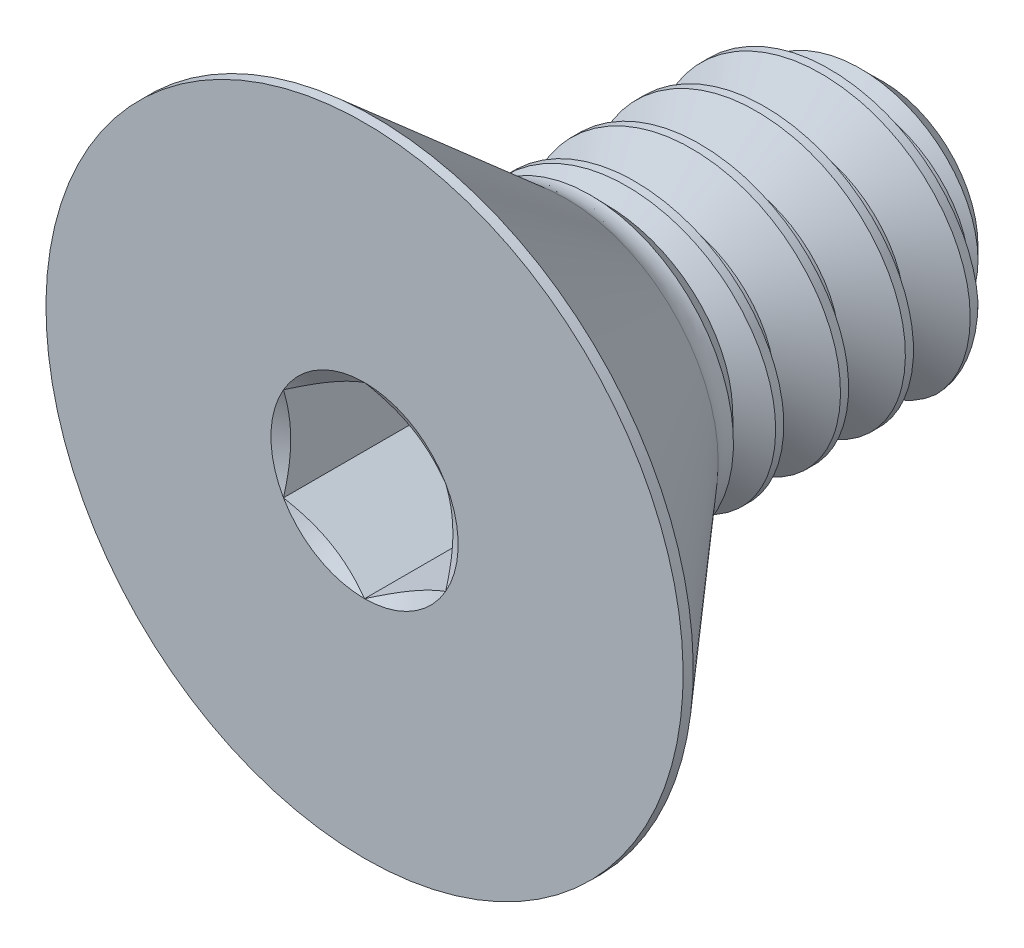
SolidWorks part; units mm, degrees
ref_plane "Front" through (0, 0, 0) normal (0, 0, 1) x (1, 0, 0)
ref_plane "Top" through (0, 0, 0) normal (0, 1, 0) x (1, 0, 0)
ref_plane "Right" through (0, 0, 0) normal (1, 0, 0) x (0, 0, -1)
sketch "Sketch1" plane through (0, 0, 0) normal (1, 0, 0) x (0, 0, -1)
  line L0 (0, 3.8989) -> (0.1232, 3.8989) construction
  line L1 (0.1232, 3.8989) -> (2.4638, 1.8642) construction
  line L2 (0, 1.7526) -> (6.35, 1.7526)
  line L3 (6.35, 1.7526) -> (6.35, 0)
  line L4 (6.35, 0) -> (0, 0)
  line L5 (0, 0) -> (0, 3.8989) construction
  line L6 (0, 3.8989) -> (0, -3.8989) construction
  line L7 (6.35, 1.7526) -> (6.35, -1.7526) construction
  line L8 (0, -3.8989) -> (0.1232, -3.8989) construction
  line L9 (0.1232, -3.8989) -> (2.4638, -1.8642) construction
  line L11 (0, 1.7526) -> (0, 0)
  line L12 (2.7624, 1.7526) -> (2.7624, 0) construction
  line L13 (-19.05, 0) -> (-19.05, 1.7526) construction
  arc A1 (2.4638, 1.8642) -> (2.7624, 1.7526) centre (2.7624, 2.2077) ccw construction
  dimension "D1" = 0.1232
  dimension "Head Ht" = 2.4638
  dimension "Head Dia" = 7.7978
  dimension "Dia" = 3.5052
  dimension "Lg" = 6.35
  dimension "Head Angle" = 82
  dimension "Min Thread" = 25.4
revolve "Revolve1" add sketch "Sketch1" angle 360 about L4
sketch "Sketch3" plane through (0, 0, -6.35) normal (0, 0, -1) x (-1, 0, 0)
  circle A0 centre (0, 0) radius 1.7526
curve "Helix/Spiral1" pitch 0.7937 height 6.35 radius 1.7526 centre (0, 0, -6.35) axis (0, 0, 1) start towards (0, 1, 0)
sketch "Sketch2" plane through (0, 0, 0) normal (1, 0, 0) x (0, 0, -1)
  line L0 (6.35, 1.7526) -> (7.0445, 1.7526)
  line L1 (7.0445, 1.7526) -> (6.7469, 1.237)
  line L2 (6.7469, 1.237) -> (6.6477, 1.237)
  line L3 (6.6477, 1.237) -> (6.35, 1.7526)
  line L4 (6.4988, 1.4948) -> (6.8957, 1.4948) construction
  dimension "D1" = 60
  dimension "D2" = 0.0992
  dimension "D3" = 0.3969
ref_plane "Plane2" through (0, 0, 19.05) normal (0, 0, 1) x (1, 0, 0)
chamfer "Chamfer1" distance 0.5953 angle 45 1 edges at (0, 1.7526, -6.35)
sweep "Cut-Sweep1" cut profiles "Sketch2" path "Helix/Spiral1"
sketch "Sketch7" plane through (0, 0, 0) normal (1, 0, 0) x (0, 0, -1)
  line L0 (0, 3.8989) -> (0.1232, 3.8989) construction
  line L1 (0.1232, 3.8989) -> (2.4638, 1.8642) construction
  line L2 (0, 3.8989) -> (0.1232, 3.8989)
  line L3 (0.1232, 3.8989) -> (2.4638, 1.8642)
  line L4 (2.7624, 1.7526) -> (2.7624, 0) construction
  line L5 (2.7624, 1.7526) -> (2.7624, 0)
  line L7 (0, 0) -> (0, 3.8989) construction
  line L8 (0, 0) -> (0, 3.8989)
  line L9 (0, 0) -> (2.7624, 0)
  line L10 (5.7417, 0) -> (-5.7417, 0) construction
  arc A0 (2.4638, 1.8642) -> (2.7624, 1.7526) centre (2.7624, 2.2077) ccw construction
  arc A1 (2.4638, 1.8642) -> (2.7624, 1.7526) centre (2.7624, 2.2077) ccw
revolve "Revolve2" add sketch "Sketch7" angle 360 about L9
ref_plane "Plane1" through (0, 0, -2.7624) normal (0, 0, 1) x (1, 0, 0)
sketch "Sketch8" plane through (0, 0, -2.7624) normal (0, 0, 1) x (1, 0, 0)
  circle A0 centre (0, 0) radius 1.7526
extrude "Boss-Extrude1" add sketch "Sketch8" against normal through all draft 46
sketch "Sketch5" plane through (0, 0, 0) normal (0, 0, 1) x (1, 0, 0)
  line L0 (0, 0) -> (-1.1457, 0) construction
  line L1 (0, 0) -> (-2.7496, 1.5875) construction
  line L2 (0, 0) -> (-2.7496, -1.5875) construction
  line L6 (0, 1.1457) -> (0, 0.9449) construction
  line L7 (0, 0.9449) -> (0, 0.7441) construction
  line L9 (0, 1.1457) -> (-0.9922, 0.5728)
  line L10 (-0.9922, 0.5728) -> (-0.9922, -0.5728)
  line L11 (-0.9922, -0.5728) -> (0, -1.1457)
  line L12 (0, -1.1457) -> (0.9922, -0.5728)
  line L13 (0.9922, -0.5728) -> (0.9922, 0.5728)
  line L14 (0.9922, 0.5728) -> (0, 1.1457)
  circle A0 centre (0, 0) radius 1.1457 construction
  circle A1 centre (0, 0) radius 0.9449 construction
  circle A2 centre (0, 0) radius 0.7441 construction
  circle A3 centre (0, 0) radius 0.9922 construction
  dimension "D3" = 1.4883
  dimension "Hex" = 1.9844
  dimension "D4" = 30
  dimension "D5" = 30
extrude "Cut-Extrude2" cut sketch "Sketch5" against normal blind 1.7247
sketch "Sketch6" plane through (0, 0, 0) normal (0, 0, 1) x (1, 0, 0)
  circle A0 centre (0, 0) radius 1.1457
extrude "Cut-Extrude3" cut sketch "Sketch6" against normal blind 1.7247 draft 60
sketch "Sketch9" [suppressed] plane through (0, 0, -3.6076) normal (0, 0, 1) x (1, 0, 0)
  circle A1 centre (0, 0) radius 2.413
  circle A2 centre (0, 0) radius 2.413
  point P0 (0, 2.413)
  dimension "D1" = 0
extrude "Boss-Extrude2" [suppressed] add sketch "Sketch9" against normal up to surface (15.4424 mm away) up to plane "Plane2"
sketch "Sketch10" plane through (0, 0, 0) normal (1, 0, 0) x (0, 0, -1)
  line L0 (6.35, 1.7526) -> (6.35, -1.7526) construction
  point P0 (5.1594, -1.7526)
  dimension "D1" = 1.1906
equation "\"D3@Helix/Spiral1\" = \"Lg@Sketch1\""
equation "\"D2@Sketch2\" = \"D4@Helix/Spiral1\" * .125"
equation "\"D3@Sketch2\" = \"D4@Helix/Spiral1\" * .5"
equation "\"D1@Chamfer1\" = \"D4@Helix/Spiral1\" * .75"
equation "\"D1@Cut-Extrude2\" = \"Head Ht@Sketch1\" * .7"
equation "\"D1@Sketch1\" = \"Head Ht@Sketch1\" * .05"
equation "\"D1@Sketch10\" = \"D4@Helix/Spiral1\" * 1.5"
equation "\"D1@Cut-Extrude3\" = \"D1@Cut-Extrude2\""
equation "\"D3@Sketch5\" = \"Hex@Sketch5\" * .75"
